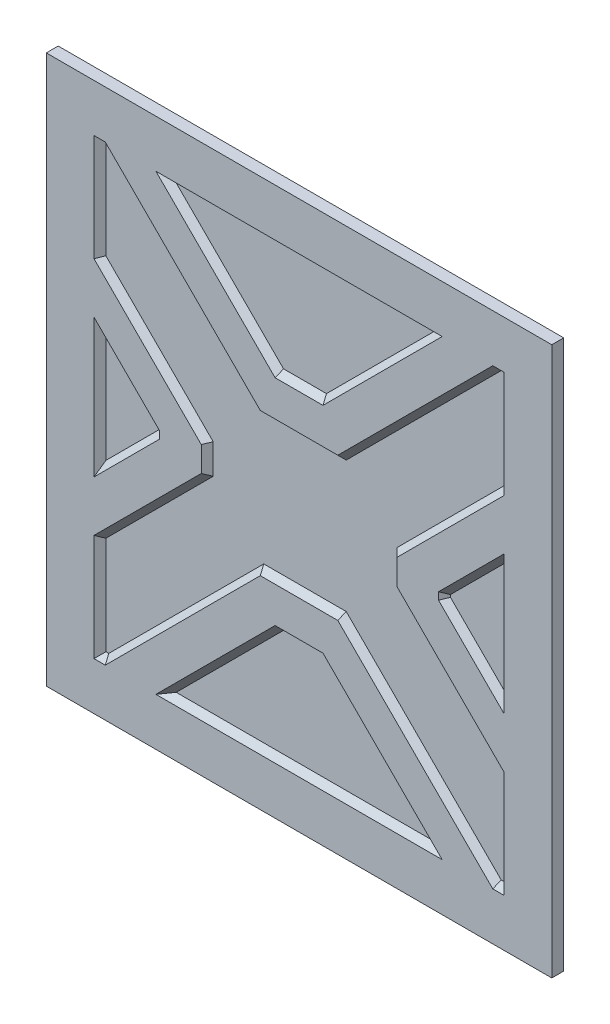
SolidWorks part; units mm, degrees
ref_plane "Plan de face" through (0, 0, 0) normal (0, 0, 1) x (1, 0, 0)
ref_plane "Plan de dessus" through (0, 0, 0) normal (0, 1, 0) x (1, 0, 0)
ref_plane "Plan de droite" through (0, 0, 0) normal (1, 0, 0) x (0, 0, -1)
sketch "Esquisse1" plane through (0, 0, 0) normal (0, 0, 1) x (1, 0, 0)
  line L1 (0, 0) -> (424, 0)
  line L2 (0, 0) -> (0, 460)
  line L3 (0, 460) -> (424, 460)
  line L4 (424, 0) -> (424, 460)
  dimension "D1" = 460
  dimension "D2" = 424
extrude "Boss.-Extru.1" add sketch "Esquisse1" along normal blind 10
sketch "Esquisse2" plane through (0, 0, 10) normal (0, 0, 1) x (1, 0, 0)
  line L0 (179.4975, 290) -> (130, 240.5025) construction
  line L1 (95, 226.9239) -> (95, 233.0761)
  line L2 (95, 233.0761) -> (40, 288.0761)
  line L3 (191.9239, 320) -> (232.0761, 320)
  line L4 (212, 420) -> (212, 40) construction
  line L5 (384, 230) -> (40, 230) construction
  line L6 (40, 420) -> (40, 330.5025)
  line L7 (40, 330.5025) -> (130, 240.5025)
  line L8 (40, 420) -> (40, 40)
  line L9 (40, 40) -> (384, 40)
  line L10 (384, 40) -> (384, 420)
  line L11 (384, 420) -> (40, 420)
  line L12 (40, 420) -> (40, 40) construction
  line L13 (40, 40) -> (384, 40) construction
  line L14 (384, 40) -> (384, 420) construction
  line L15 (384, 420) -> (40, 420) construction
  line L16 (130, 240.5025) -> (130, 219.4975)
  line L17 (40, 420) -> (49.4975, 420)
  line L18 (49.4975, 420) -> (179.4975, 290)
  line L19 (244.5025, 290) -> (179.4975, 290)
  line L20 (332.0761, 420) -> (91.9239, 420)
  line L21 (91.9239, 420) -> (191.9239, 320)
  line L22 (294, 240.5025) -> (294, 219.4975)
  line L23 (40, 288.0761) -> (40, 171.9239)
  line L24 (329, 226.9239) -> (329, 233.0761)
  line L25 (130, 240.5025) -> (130, 290) construction
  line L26 (130, 290) -> (179.4975, 290) construction
  line L27 (329, 233.0761) -> (384, 288.0761)
  line L28 (384, 288.0761) -> (384, 171.9239)
  line L29 (384, 330.5025) -> (294, 240.5025)
  line L30 (384, 420) -> (384, 330.5025)
  line L31 (384, 420) -> (374.5025, 420)
  line L32 (374.5025, 420) -> (244.5025, 290)
  line L33 (332.0761, 420) -> (232.0761, 320)
  line L34 (95, 226.9239) -> (40, 171.9239)
  line L35 (40, 129.4975) -> (130, 219.4975)
  line L36 (384, 40) -> (374.5025, 40)
  line L37 (384, 40) -> (384, 129.4975)
  line L38 (40, 40) -> (40, 129.4975)
  line L39 (40, 40) -> (49.4975, 40)
  line L40 (332.0761, 40) -> (91.9239, 40)
  line L41 (191.9239, 140) -> (232.0761, 140)
  line L42 (244.5025, 170) -> (179.4975, 170)
  line L43 (91.9239, 40) -> (191.9239, 140)
  line L44 (49.4975, 40) -> (179.4975, 170)
  line L45 (332.0761, 40) -> (232.0761, 140)
  line L46 (374.5025, 40) -> (244.5025, 170)
  line L47 (384, 129.4975) -> (294, 219.4975)
  line L48 (329, 226.9239) -> (384, 171.9239)
  point P20 (212, 290)
  point P23 (294, 230)
  point P31 (212, 320)
  point P33 (95, 230)
  point P34 (130, 230)
  point P47 (329, 230)
  dimension "D2" = 90
  dimension "D3" = 130
  dimension "D4" = 70
  dimension "D5" = 45
  dimension "D6" = 30
  dimension "D7" = 35
  dimension "D8" = 30
  dimension "D9" = 30
  dimension "D1" = 40
extrude "Enlèv. mat.-Extru.1" cut sketch "Esquisse2" against normal blind 5
chamfer "Chanfrein1" distance 5 angle 45 36 edges at (212, 40, 5) (141.9239, 90, 5) (212, 140, 5) (282.0761, 90, 5) (40, 230, 5) (67.5, 260.5761, 5) (95, 230, 5) (67.5, 199.4239, 5) (384, 230, 5) (356.5, 199.4239, 5) (329, 230, 5) (356.5, 260.5761, 5) (114.4975, 355, 5) (212, 290, 5) (309.5025, 355, 5) (379.2513, 420, 5) (384, 375.2513, 5) (339, 285.5025, 5) (294, 230, 5) (339, 174.4975, 5) (384, 84.7487, 5) (379.2513, 40, 5) (309.5025, 105, 5) (212, 170, 5) (114.4975, 105, 5) (44.7487, 40, 5) (40, 84.7487, 5) (85, 174.4975, 5) (130, 230, 5) (85, 285.5025, 5) (40, 375.2513, 5) (44.7487, 420, 5) (212, 420, 5) (282.0761, 370, 5) (212, 320, 5) (141.9239, 370, 5)
